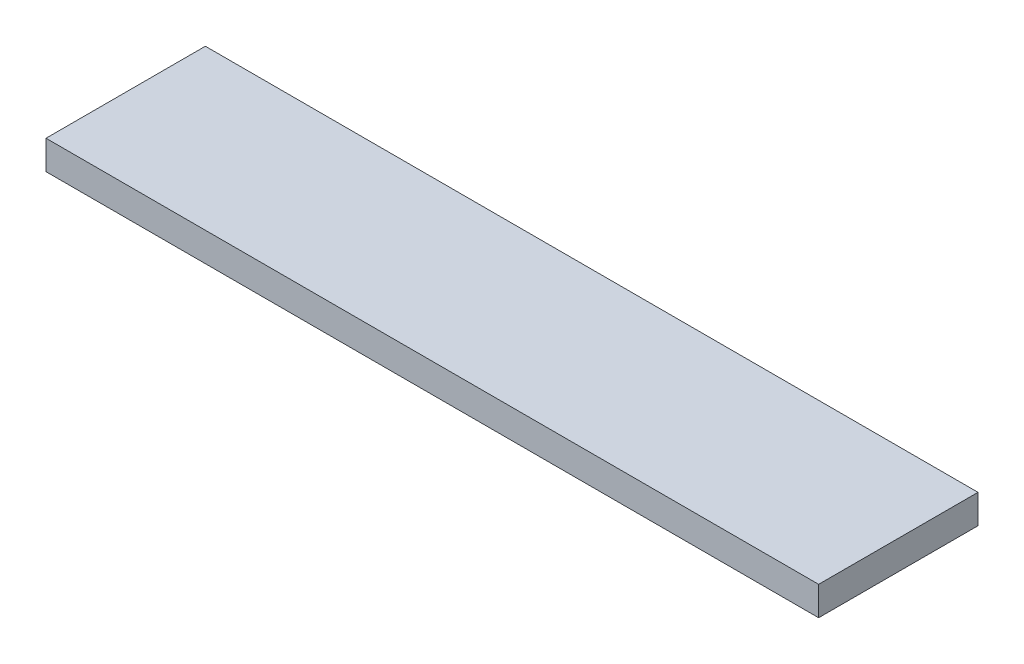
SolidWorks part; units mm, degrees
ref_plane "Front Plane" through (0, 0, 0) normal (0, 0, 1) x (1, 0, 0)
ref_plane "Top Plane" through (0, 0, 0) normal (0, 1, 0) x (1, 0, 0)
ref_plane "Right Plane" through (0, 0, 0) normal (1, 0, 0) x (0, 0, -1)
sketch "Sketch1" plane through (0, 0, 0) normal (0, 1, 0) x (1, 0, 0)
  line L0 (80, -80) -> (80, 0) construction
  line L1 (0, 0) -> (80, 0)
  line L2 (0, 0) -> (0, -16.5)
  line L3 (0, -16.5) -> (80, -16.5)
  line L4 (80, 0) -> (80, -16.5)
sketch "Sketch2" plane through (0, 0, 0) normal (1, 0, 0) x (0, 0, -1)
  line L1 (0, 0) -> (-16.5, 0)
  line L2 (0, 0) -> (0, -3)
  line L3 (0, -3) -> (-16.5, -3)
  line L4 (-16.5, 0) -> (-16.5, -3)
extrude "Boss-Extrude1" add sketch "Sketch1" against normal up to vertex (3 mm away) up to point (0, -3, 0)
